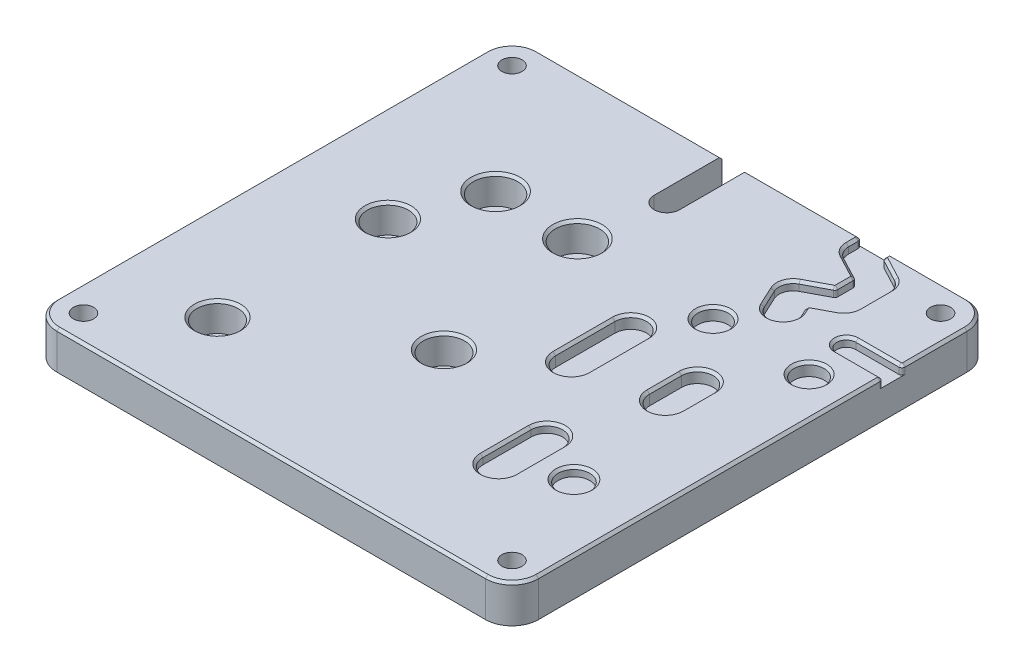
SolidWorks part; units mm, degrees
ref_plane "Front Plane" through (0, 0, 0) normal (0, 0, 1) x (1, 0, 0)
ref_plane "Top Plane" through (0, 0, 0) normal (0, 1, 0) x (1, 0, 0)
ref_plane "Right Plane" through (0, 0, 0) normal (1, 0, 0) x (0, 0, -1)
sketch "Base plate" plane through (0, 0, 0) normal (0, 1, 0) x (1, 0, 0)
  line L0 (-2.9, 38.1) -> (-2.9, 27.4) construction
  line L1 (-33.9, -38.1) -> (33.9, -38.1)
  line L2 (-38.1, -33.9) -> (-38.1, 33.9)
  line L3 (-33.9, 38.1) -> (33.9, 38.1)
  line L4 (38.1, -33.9) -> (38.1, 33.9)
  line L5 (-38.1, -38.1) -> (38.1, 38.1) construction
  line L6 (-38.1, 38.1) -> (38.1, -38.1) construction
  line L7 (-0.9, 38.1) -> (-0.9, 27.4)
  line L8 (-4.9, 38.1) -> (-4.9, 27.4)
  circle A0 centre (-33.9, 33.9) radius 1.6
  circle A1 centre (33.9, 33.9) radius 1.6
  circle A2 centre (33.9, -33.9) radius 1.6
  circle A3 centre (-33.9, -33.9) radius 1.6
  arc A4 (-33.9, -38.1) -> (-38.1, -33.9) centre (-33.9, -33.9) cw
  arc A5 (33.9, -38.1) -> (38.1, -33.9) centre (33.9, -33.9) ccw
  arc A6 (33.9, 38.1) -> (38.1, 33.9) centre (33.9, 33.9) cw
  arc A7 (-38.1, 33.9) -> (-33.9, 38.1) centre (-33.9, 33.9) cw
  arc A9 (-4.9, 27.4) -> (-0.9, 27.4) centre (-2.9, 27.4) ccw
  point P0 (0, 0)
  dimension "D2" = 3.2
  dimension "D4" = 4.2
  dimension "D5" = 2
  dimension "D6" = 12.7
  dimension "D1" = 76.2
  dimension "D3" = 4.2
  dimension "D7" = 39
extrude "凸台-拉伸1" add sketch "Base plate" along normal blind 6 contours A9 L8 L3 A7 L2 A4 L1 A5 L4 A6 L7 A3 A2 A1 A0 region at (0.0249, 0, 0.2747)
fillet "圆角1" [suppressed] radius 1
sketch "草图1" plane through (0, 0, 0) normal (0, -1, 0) x (1, 0, 0)
  line L0 (456, 1824) -> (2280, 1824) construction
  line L1 (-33.9, -33.9) -> (33.9, -33.9) construction
  line L3 (-0.35, 10.415) -> (-22.7, 10.415) construction
  line L6 (11.4, 2) -> (11.4, -7.4) construction
  line L7 (13.9, 2) -> (13.9, -7.4)
  line L8 (8.9, 2) -> (8.9, -7.4)
  line L9 (24.1, -0.16) -> (24.1, -5.24) construction
  line L10 (26.6, -0.16) -> (26.6, -5.24)
  line L11 (21.6, -0.16) -> (21.6, -5.24)
  line L12 (24.1, -2.7) -> (11.4, -2.7) construction
  line L13 (19.6, 21.71) -> (19.6, 14.09) construction
  line L14 (22.1, 21.71) -> (22.1, 14.09)
  line L15 (17.1, 21.71) -> (17.1, 14.09)
  line L16 (30.8, -22.1) -> (38.1, -22.1) construction
  line L17 (30.8, -20.6) -> (38.1, -20.6)
  line L18 (30.8, -23.6) -> (38.1, -23.6)
  line L19 (27.7, 17.9) -> (19.6, 17.9) construction
  line L24 (16.7, -15.1) -> (31.9, -15.1) construction
  line L25 (38.1, -20.6) -> (38.1, -23.6)
  line L26 (24.4, -28.1) -> (24.4, -33.1) construction
  line L27 (26.65, -28.1) -> (26.65, -33.1)
  line L28 (22.15, -28.1) -> (22.15, -33.1)
  line L29 (20.8, -22.1) -> (19.4, -25.1) construction
  line L30 (22.8389, -23.0515) -> (21.4389, -26.0515)
  line L31 (18.7611, -21.1485) -> (17.3611, -24.1485)
  line L32 (19.4, -36.1) -> (19.4, -38.1) construction
  line L33 (-0.9, -38.1) -> (33.9, -38.1) construction
  line L34 (21.65, -36.1) -> (21.65, -38.1)
  line L35 (17.15, -36.1) -> (17.15, -38.1)
  line L36 (17.15, -38.1) -> (21.65, -38.1)
  line L37 (24.4, -30.6) -> (19.4, -30.6) construction
  line L38 (19.4, -25.1) -> (19.4, -36.1) construction
  line L39 (30.8, -22.1) -> (20.8, -22.1) construction
  line L40 (18.348, -34.1111) -> (22.15, -32.1)
  line L41 (25.452, -35.0889) -> (21.65, -37.1)
  line L42 (18.348, -27.0889) -> (22.15, -29.1)
  line L43 (25.452, -26.1111) -> (22.2111, -24.3968)
  line L44 (-22.7, 23.9) -> (-22.7, -3.07) construction
  line L46 (-33.9, -38.1) -> (33.9, -38.1) construction
  line L48 (38.1, 33.9) -> (38.1, -33.9) construction
  line L49 (-33.9, 38.1) -> (33.9, 38.1) construction
  line L50 (-38.1, 33.9) -> (-38.1, -33.9) construction
  circle A0 centre (-22.7, 23.9) radius 3.25
  circle A1 centre (-0.35, 10.415) radius 3.25
  circle A2 centre (-22.7, -3.07) radius 3.25
  circle A3 centre (-17.96, -15.36) radius 3.5
  circle A4 centre (-5.01, -15.36) radius 3.5
  arc A8 (13.9, 2) -> (8.9, 2) centre (11.4, 2) ccw
  arc A9 (8.9, -7.4) -> (13.9, -7.4) centre (11.4, -7.4) ccw
  arc A10 (26.6, -0.16) -> (21.6, -0.16) centre (24.1, -0.16) ccw
  arc A11 (21.6, -5.24) -> (26.6, -5.24) centre (24.1, -5.24) ccw
  circle A12 centre (27.7, 17.9) radius 2.5
  arc A13 (22.1, 21.71) -> (17.1, 21.71) centre (19.6, 21.71) ccw
  arc A14 (17.1, 14.09) -> (22.1, 14.09) centre (19.6, 14.09) ccw
  arc A15 (30.8, -20.6) -> (30.8, -23.6) centre (30.8, -22.1) ccw
  circle A21 centre (16.7, -15.1) radius 2.4
  circle A22 centre (31.9, -15.1) radius 2.4
  arc A25 (26.65, -28.1) -> (22.15, -28.1) centre (24.4, -28.1) ccw
  arc A26 (22.15, -33.1) -> (26.65, -33.1) centre (24.4, -33.1) ccw
  arc A27 (22.8389, -23.0515) -> (18.7611, -21.1485) centre (20.8, -22.1) ccw
  arc A28 (17.3611, -24.1485) -> (21.4389, -26.0515) centre (19.4, -25.1) ccw
  arc A29 (21.65, -36.1) -> (17.15, -36.1) centre (19.4, -36.1) ccw
  point P21 (11.4, -2.7)
  point P26 (24.1, -2.7)
  point P39 (19.6, 17.9)
  point P61 (24.4, -30.6)
  point P70 (20.1, -23.6)
  point P95 (-22.7, 10.415)
  point P98 (37.3942, -22.1)
  point P99 (0, 0)
  point P101 (38.1, -22.1)
  point P102 (37.2017, -22.1)
  point P104 (37.2017, -20.6)
  line M4 (-0.9, -38.1) -> (33.9, -38.1)
  line M6 (38.1, -33.9) -> (38.1, 33.9)
  dimension "D1" = 6.5
  dimension "D7" = 7
  dimension "D10" = 2.5
  dimension "D11" = 5
  dimension "D12" = 2.5
  dimension "D13" = 4.8
  dimension "D20" = 6.2
  dimension "D21" = 11.8
  dimension "D24" = 5.08
  dimension "D31" = 2.25
  dimension "D33" = 9.5
  dimension "D36" = 8.8
  dimension "D2" = 26.97
  dimension "D4" = 22.35
  dimension "D5" = 14.2
  dimension "D6" = 12.95
  dimension "D8" = 4.74
  dimension "D9" = 12.29
  dimension "D14" = 15.2
  dimension "D15" = 8.1
  dimension "D16" = 7.62
  dimension "D17" = 9.4
  dimension "D18" = 12.7
  dimension "D19" = 3
  dimension "D22" = 18.8
  dimension "D23" = 14
  dimension "D25" = 31.2
  dimension "D26" = 16
  dimension "D27" = 14.3
  dimension "D28" = 5
  dimension "D29" = 4.5
  dimension "D30" = 5
  dimension "D32" = 11
  dimension "D34" = 5
  dimension "D35" = 10
  dimension "D37" = 15.4
extrude "切除-拉伸1" cut sketch "草图1" along normal blind 4.5 from surface contours A1 | A0 | A2 | A3 | A4 region at (-22.7, 0, 23.9) region at (-0.35, 0, 10.415) starting at face at (-0.9667, 6, -10.75)
extrude "切除-拉伸2" cut sketch "草图1<6>" along normal blind 2 from surface contours L8 A9 L7 A8 | L11 A11 L10 A10 | A22 | A21 region at (11.4, 0, -2.7) region at (24.1, 0, -2.7) starting at face at (-5.01, 6, -11.86)
sketch "草图1<6>" plane through (0, 0, 0) normal (0, -1, 0) x (1, 0, 0) same geometry as "草图1"
extrude "切除-拉伸3" cut sketch "草图1<7>" along normal blind 1.4 from surface contours L34 A29 L35 M4 | A29 L34 L41 A26 L28 L40 | A26 L27 A25 L28 | A28 L42 L28 A25 L43 L30 | L31 A28 L30 A27 | L17 A15 L18 M6 | L15 A14 L14 A13 | A12 region at (19.6, 0, 17.9) region at (33.8543, 0, -22.1) region at (24.4, 0, -30.6) region at (21.9038, 0, -26.6982) region at (21.9, 0, -34.6) region at (20.1, 0, -23.6) region at (19.4, 0, -36.183) region at (27.7, 0, 17.9) starting at face at (31.9, 6, -12.7)
sketch "草图1<7>" plane through (0, 0, 0) normal (0, -1, 0) x (1, 0, 0) same geometry as "草图1"
fillet "圆角2" radius 0.5 8 edges at (21.65, 5.3, -38.1) (17.15, 5.3, -38.1) (38.1, 5.3, -23.6) (38.1, 5.3, -20.6) (21.65, 5.3, -37.1) (22.15, 5.3, -32.1) (22.15, 5.3, -29.1) (22.2111, 5.3, -24.3968)
chamfer "倒角1" distance 0.4 angle 45 57 edges at (17.1, 6, 17.9) (19.6, 6, 24.21) (22.1, 6, 17.9) (19.6, 6, 11.59) (8.9, 6, -2.7) (11.4, 6, 4.5) (13.9, 6, -2.7) (11.4, 6, -9.9) (21.6, 6, -2.7) (24.1, 6, 2.34) (26.6, 6, -2.7) (24.1, 6, -7.74) (-0.35, 6, 13.665) (-22.7, 6, 27.15) (-22.7, 6, 0.18) (-17.96, 6, -11.86) (-5.01, 6, -11.86) (31.9, 6, -12.7) (27.7, 6, 20.4) (16.7, 6, -12.7) (29.3, 6, -22.1) (0, 6, 38.1) (-36.8698, 6, 36.8698) (36.8698, 6, 36.8698) (-38.1, 6, 0) (38.1, 6, 6.9) (-36.8698, 6, -36.8698) (37.9536, 6, -20.4536) (-19.4, 6, -38.1) (34.2, 6, -20.6) (34.2, 6, -23.6) (37.9536, 6, -23.7464) (38.1, 6, -29) (36.8698, 6, -36.8698) (7.875, 6, -38.1) (28.025, 6, -38.1) (17.0036, 6, -37.9536) (21.7964, 6, -37.9536) (17.15, 6, -36.85) (21.65, 6, -37.5006) (17.4726, 6, -34.9391) (21.7217, 6, -37.1432) (20.1159, 6, -33.176) (23.6841, 6, -36.024) (22.0783, 6, -32.0568) (26.3274, 6, -34.2609) (22.15, 6, -30.6) (26.65, 6, -30.6) (22.0783, 6, -29.1432) (26.3274, 6, -26.9391) (20.1159, 6, -28.024) (24.0418, 6, -25.3651) (17.2669, 6, -25.8159) (22.3913, 6, -24.3363) (18.0611, 6, -22.6485) (22.6256, 6, -23.5086) (21.7515, 6, -20.0611)
